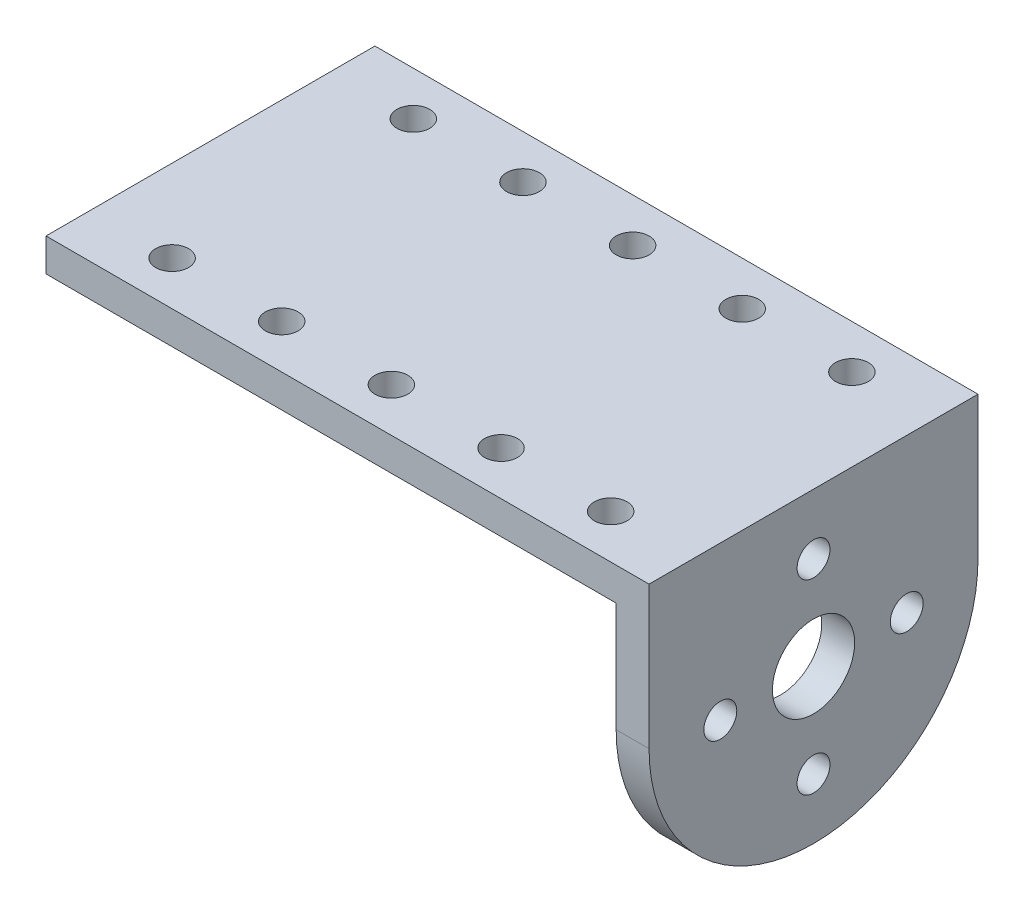
SolidWorks part; units mm, degrees
ref_plane "Front Plane" through (0, 0, 0) normal (0, 0, 1) x (1, 0, 0)
ref_plane "Top Plane" through (0, 0, 0) normal (0, 1, 0) x (1, 0, 0)
ref_plane "Right Plane" through (0, 0, 0) normal (1, 0, 0) x (0, 0, -1)
sketch "Sketch1" plane through (0, 0, 0) normal (0, 1, 0) x (1, 0, 0)
  line L0 (-27.5, 0) -> (27.5, 0) construction
  line L1 (-27.5, 15) -> (27.5, 15)
  line L2 (-27.5, 15) -> (-27.5, -15)
  line L3 (-27.5, -15) -> (27.5, -15)
  line L4 (27.5, 15) -> (27.5, -15)
  line L5 (-27.5, 15) -> (27.5, -15) construction
  line L6 (-27.5, -15) -> (27.5, 15) construction
  line L7 (-27.5, 11) -> (-20, 11) construction
  line L8 (20, 11) -> (27.5, 11) construction
  circle A0 centre (20, 11) radius 1.5
  circle A1 centre (10, 11) radius 1.5
  circle A2 centre (0, 11) radius 1.5
  circle A3 centre (-10, 11) radius 1.5
  circle A4 centre (-20, 11) radius 1.5
  circle A5 centre (20, -11) radius 1.5
  circle A6 centre (10, -11) radius 1.5
  circle A7 centre (0, -11) radius 1.5
  circle A8 centre (-10, -11) radius 1.5
  circle A9 centre (-20, -11) radius 1.5
  point P0 (0, 0)
  dimension "D4" = 3
  dimension "D1" = 30
  dimension "D2" = 55
  dimension "D3" = 4
  dimension "D6" = 5
extrude "Boss-Extrude1" add sketch "Sketch1" along normal blind 3
sketch "Sketch2" plane through (0, 0, 0) normal (0, -1, 0) x (1, 0, 0)
  line L0 (27.5, -15) -> (-27.5, -15) construction
  line L1 (27.5, 15) -> (24.5, 15)
  line L2 (27.5, 15) -> (27.5, -15)
  line L3 (27.5, -15) -> (24.5, -15)
  line L4 (24.5, 15) -> (24.5, -15)
  dimension "D1" = 3
extrude "Boss-Extrude2" add sketch "Sketch2" along normal blind 25
sketch "Sketch3" plane through (27.5, 0, 0) normal (1, 0, 0) x (0, 0, -1)
  line L0 (0, -25) -> (0, 3) construction
  line L1 (15, -25) -> (-15, -25) construction
  line L2 (-15, 3) -> (15, 3) construction
  circle A0 centre (0, -11) radius 8.5 construction
  circle A1 centre (0, -19.5) radius 1.5
  circle A2 centre (-8.5, -11) radius 1.5
  circle A3 centre (0, -2.5) radius 1.5
  circle A4 centre (8.5, -11) radius 1.5
  circle A5 centre (0, -11) radius 3.75
  dimension "D1" = 17
  dimension "D2" = 3
  dimension "D3" = 7.5
extrude "Cut-Extrude1" cut sketch "Sketch3" against normal up to surface (3 mm away) up to face at (24.5, -12.5, 0)
fillet "Fillet1" radius 15 2 edges at (26, -25, -15) (26, -25, 15)
